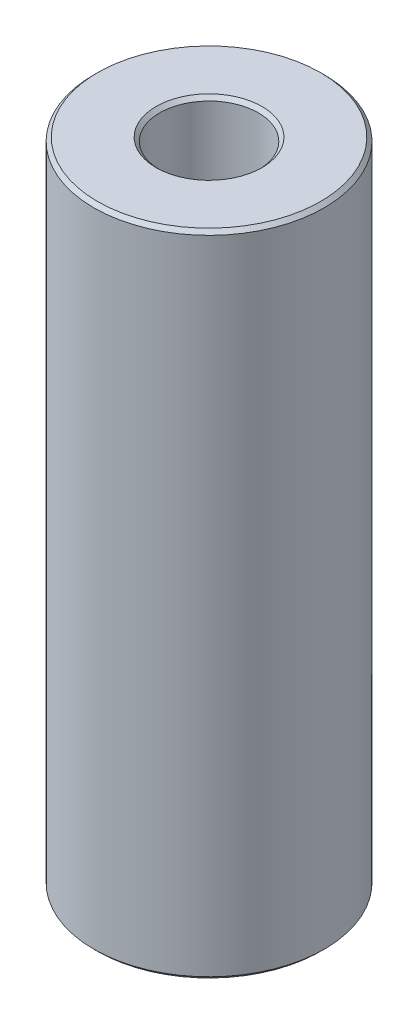
SolidWorks part; units mm, degrees
ref_plane "Front Plane" through (0, 0, 0) normal (0, 0, 1) x (1, 0, 0)
ref_plane "Top Plane" through (0, 0, 0) normal (0, 1, 0) x (1, 0, 0)
ref_plane "Right Plane" through (0, 0, 0) normal (1, 0, 0) x (0, 0, -1)
sketch "Sketch1" plane through (0, 0, 0) normal (0, 1, 0) x (1, 0, 0)
  circle A0 centre (0, 0) radius 40
  dimension "SLEEVE_OD" = 80
extrude "Boss-Extrude1" add sketch "Sketch1" along normal blind 225.4269
sketch "Sketch2" plane through (0, 0, 0) normal (0, 1, 0) x (1, 0, 0)
  circle A0 centre (0, 0) radius 17.1307
  dimension "BORE_D" = 34.2614
extrude "Cut-Extrude1" cut sketch "Sketch2" along normal through all
chamfer "Chamfer1" distance 1.2672 angle 45 4 edges at (0, 225.4269, 17.1307) (0, 0, 17.1307) (0, 0, 40) (0, 225.4269, 40)
